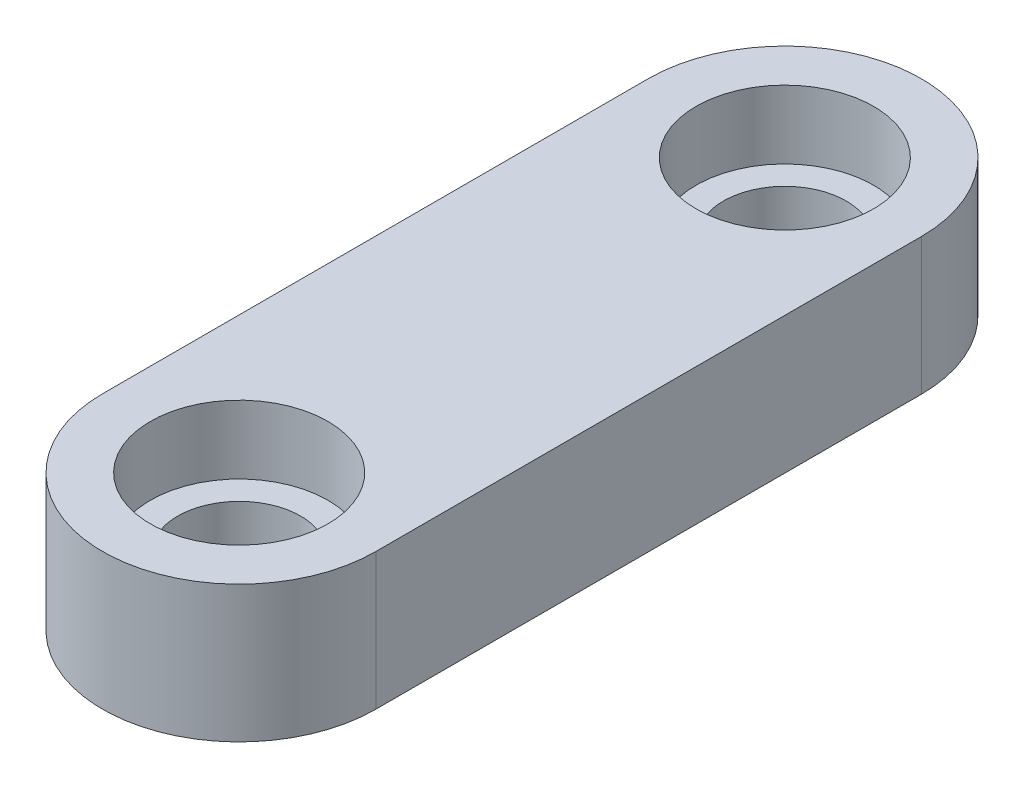
SolidWorks part; units mm, degrees
ref_plane "정면" through (0, 0, 0) normal (0, 0, 1) x (1, 0, 0)
ref_plane "윗면" through (0, 0, 0) normal (0, 1, 0) x (1, 0, 0)
ref_plane "우측면" through (0, 0, 0) normal (1, 0, 0) x (0, 0, -1)
sketch "스케치1" plane through (0, 0, 0) normal (0, 0, 1) x (1, 0, 0)
  line L1 (-10, -5) -> (10, -5)
  line L2 (-10, -5) -> (-10, 5)
  line L3 (-10, 5) -> (10, 5)
  line L4 (10, -5) -> (10, 5)
  line L5 (-10, -5) -> (10, 5) construction
  line L6 (-10, 5) -> (10, -5) construction
  point P0 (0, 0)
  dimension "D1" = 10
  dimension "D2" = 20
extrude "보스-돌출1" add sketch "스케치1" along normal blind 59.9396
sketch "스케치2" plane through (0, 5, 0) normal (0, 1, 0) x (1, 0, 0)
  line L0 (10, 0) -> (-10, 0) construction
  circle A0 centre (0, -10) radius 6.5
  dimension "D1" = 13
  dimension "D2" = 10
extrude "컷-돌출1" cut sketch "스케치2" against normal blind 5
ref_plane "평면1" through (0, 0, 29.9698) normal (0, 0, 1) x (1, 0, 0)
sketch "스케치3" plane through (0, 5, 0) normal (0, 1, 0) x (1, 0, 0)
  line L0 (-22.6352, -10) -> (28.5035, -10) construction
  line L1 (-21.2621, -10) -> (-10, -10)
  line L2 (10, -10) -> (21.2621, -10)
  circle A0 centre (0, -10) radius 4.5
  circle A1 centre (0, -10) radius 6.5
  circle A2 centre (0, -10) radius 6.5 construction
  arc A3 (10, -10) -> (-10, -10) centre (0, -10) ccw
  arc A4 (21.2621, -10) -> (-21.2621, -10) centre (0, -10) ccw
  line M5 (10, 0) -> (-10, 0)
  line M6 (-10, 0) -> (-10, -59.9396)
  line M8 (10, -59.9396) -> (10, 0)
  dimension "D2" = 9
  dimension "D1" = 0
extrude "컷-돌출2" cut sketch "스케치3" against normal blind 20 contours A0
extrude "컷-돌출3" cut sketch "스케치3<4>" against normal blind 10 contours A3 M5 M6 | A3 M8 M5 region at (-7.7663, 5, 2.2337) region at (7.7663, 5, 2.2337)
sketch "스케치3<4>" plane through (0, 5, 0) normal (0, 1, 0) x (1, 0, 0) same geometry as "스케치3"
mirror "대칭 복사1" about plane through (0, 0, 29.9698) normal (0, 0, 1) of "컷-돌출3", "컷-돌출1", "컷-돌출2"
sketch "스케치4" plane through (0, -5, 0) normal (0, 1, 0) x (1, 0, 0)
  line L0 (-3.7446, -37.3853) -> (-10, -33.7738)
  line L2 (0, -5.5) -> (0, 5.5) construction
  line L3 (-10, -49.9396) -> (-10, -10) construction
  line L4 (-10, -33.7738) -> (-10, -29.7476)
  line L7 (0, -49.9396) -> (-13.5316, -42.1271) construction
  line L8 (0, -29.7476) -> (-10, -29.7476)
  line L11 (-3.7446, -33.8404) -> (0, -33.8404)
  line L12 (0, -29.7476) -> (0, -33.8404)
  line L13 (-3.7446, -33.8404) -> (-3.7446, -37.3853)
  circle A2 centre (0, -49.9396) radius 4.5 construction
  dimension "D1" = 120
  dimension "D2" = 9
extrude "보스-돌출2" add sketch "스케치4" against normal blind 5
sketch "스케치5" plane through (0, -5, 0) normal (0, -1, 0) x (1, 0, 0)
  line L1 (-7, 29.7476) -> (-3.8916, 29.7476)
  line L2 (-7, 29.7476) -> (-7, 21.7476)
  line L3 (-7, 21.7476) -> (-3.8916, 21.7476)
  line L4 (-3.8916, 29.7476) -> (-3.8916, 21.7476)
  line L5 (-10, 29.7476) -> (-10, 10) construction
  point P10 (0, 0)
  dimension "D1" = 8
  dimension "D2" = 3
extrude "컷-돌출4" cut sketch "스케치5" against normal blind 8
sketch "스케치7" plane through (-7, 0, 0) normal (1, 0, 0) x (0, 0, -1)
  line L0 (-25.7476, -5) -> (-25.7476, 3) construction
  line L1 (-29.7476, -5) -> (-21.7476, -5) construction
  line L2 (-29.7476, 3) -> (-21.7476, 3) construction
  circle A0 centre (-23.6893, -1) radius 1.25
  circle A1 centre (-27.8059, -1) radius 1.25
  dimension "D1" = 2.5
extrude "컷-돌출5" cut sketch "스케치7" against normal blind 8
